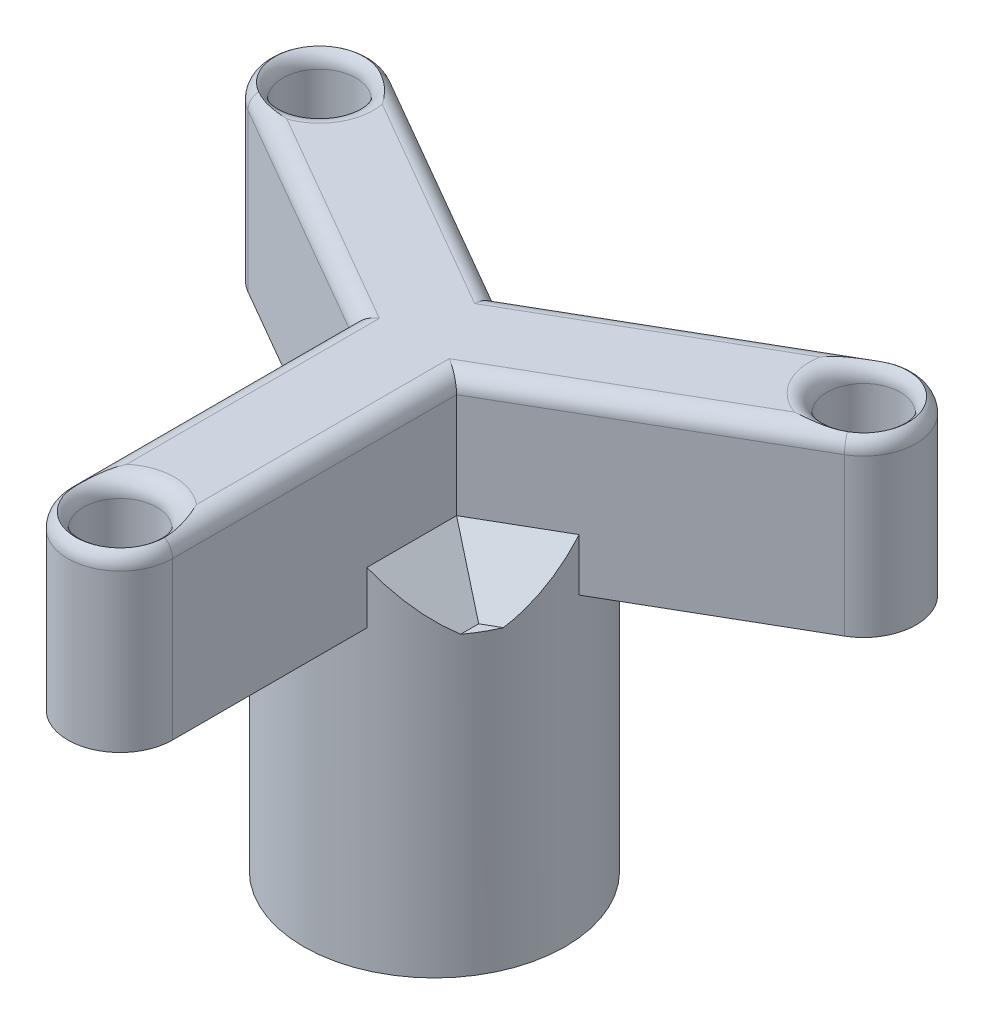
SolidWorks part; units mm, degrees
ref_plane "Front Plane" through (0, 0, 0) normal (0, 0, 1) x (1, 0, 0)
ref_plane "Top Plane" through (0, 0, 0) normal (0, 1, 0) x (1, 0, 0)
ref_plane "Right Plane" through (0, 0, 0) normal (1, 0, 0) x (0, 0, -1)
sketch "Sketch1" plane through (0, 0, 0) normal (0, 1, 0) x (1, 0, 0)
  circle A0 centre (0, 0) radius 7.5
  circle A1 centre (0, 0) radius 2.575
  dimension "D1" = 15
  dimension "D2" = 5.15
extrude "Boss-Extrude1" add sketch "Sketch1" along normal blind 15
sketch "Sketch2" plane through (0, 0, 0) normal (0, 0, 1) x (1, 0, 0)
  line L1 (0, 7.5) -> (0, 15) construction
  line L2 (0, 7.5) -> (0, 0) construction
  circle A0 centre (0, 7.5) radius 1.25
  dimension "D1" = 2.5
extrude "Cut-Extrude1" cut sketch "Sketch2" against normal through all contours A0
ref_plane "Plane1" through (0, 0, -7.5) normal (0, 0, -1) x (-1, 0, 0)
thread "Thread1" pitch 0.5 method cut profile "Thread Profile1" start angle 0, offset 1, length 7, pitch 0.5, diameter 2.5
ref_plane "Plane2" through (1.25, 7.5, -8.5) normal (0, -1, 0) x (1, 0, 0)
sketch "Thread Profile1" plane through (1.25, 7.5, -8.5) normal (0, -1, 0) x (1, 0, 0)
  line L0 (0, 0) -> (0, 0.5) construction
  line L1 (0, 0) -> (0.2706, 0.1562)
  line L2 (0.2706, 0.1562) -> (0.2706, 0.2187)
  line L3 (0.2706, 0.2187) -> (0, 0.375)
  line L4 (0.2706, 0.1875) -> (0, 0.1875) construction
  line L11 (0, 0) -> (0, 0.375)
  point P2 (0, 0)
  dimension "Pitch" = 0.5
  dimension "Profile_Angle" = 60
  dimension "Profile_Land" = 0.0625
  dimension "Profile_Height" = 0.2706
sketch "Sketch12" plane through (0, 15, 0) normal (0, 1, 0) x (1, 0, 0)
  circle A0 centre (0, 0) radius 7.5
extrude "Boss-Extrude3" add sketch "Sketch12" along normal blind 2
sketch "Sketch5" plane through (0, 0, -7.5) normal (0, 0, -1) x (-1, 0, 0)
  circle A0 centre (0, 7.5) radius 1.75
  dimension "D1" = 3.5
extrude "Cut-Extrude2" cut sketch "Sketch5" against normal blind 10 draft 45
sketch "Sketch10" plane through (0, 17, 0) normal (0, 1, 0) x (1, 0, 0)
  circle A0 centre (0, 0) radius 7.5
sketch "Sketch11" plane through (0, 17, 0) normal (0, 1, 0) x (1, 0, 0)
  line L0 (0, 0) -> (-15.5885, 9) construction
  line L1 (-15.5885, 9) -> (0, 9) construction
  line L2 (0, 9) -> (0, 0) construction
  line L3 (-15.5885, 9) -> (0, 0) construction
  line L4 (-14.0885, 11.5981) -> (1.5, 2.5981)
  line L5 (-17.0885, 6.4019) -> (-1.5, -2.5981)
  arc A0 (-14.0885, 11.5981) -> (-17.0885, 6.4019) centre (-15.5885, 9) ccw
  arc A1 (-1.5, -2.5981) -> (1.5, 2.5981) centre (0, 0) ccw
  circle A2 centre (-15.5885, 9) radius 2.1
  point P3 (-7.7942, 4.5)
  dimension "D4" = 4.2
  dimension "D1" = 60
  dimension "D2" = 18
  dimension "D3" = 6
extrude "Boss-Extrude2" add sketch "Sketch11" along normal blind 10
ref_axis "Axis1" through (0, 18.9, 0) along (0, -1, 0)
pattern_circular "CirPattern1" count 3 every 120 about axis through (0, 18.9, 0) along (0, -1, 0) of "Boss-Extrude2"
chamfer "Chamfer1" distance 3 angle 45 6 edges at (-5.2265, 17, 0.4466) (-3, 17, 4.303) (3, 17, 4.303) (5.2265, 17, 0.4466) (-2.2265, 17, -4.7496) (2.2265, 17, -4.7496)
fillet "Fillet1" radius 1 12 edges at (-10.0442, 27, -2.3349) (-18.1865, 27, -10.5) (7.0442, 27, -7.5311) (18.1865, 27, -10.5) (-3, 27, 9.866) (0, 27, 21) (-7.0442, 27, -7.5311) (10.0442, 27, -2.3349) (3, 27, 9.866) (1.8187, 27, 16.95) (-15.5885, 27, -6.9) (13.7698, 27, -10.05)
